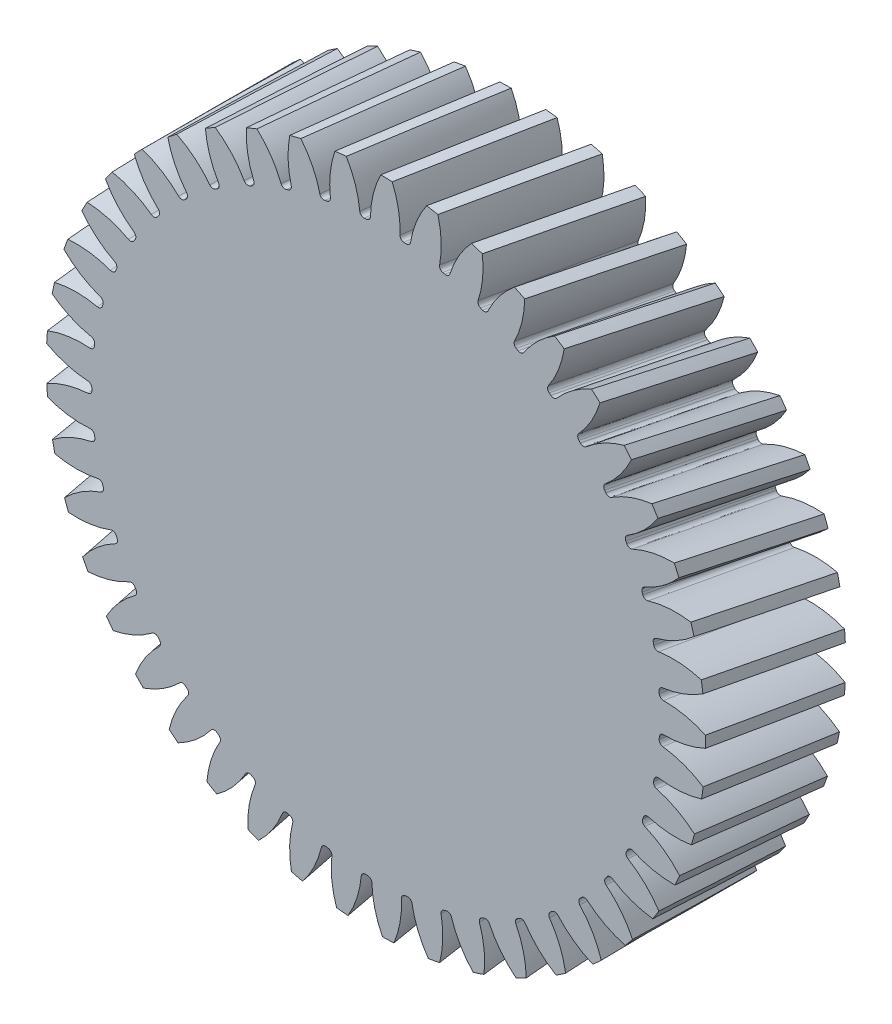
SolidWorks part; units mm, degrees
ref_plane "Front Plane" through (0, 0, 0) normal (0, 0, 1) x (1, 0, 0)
ref_plane "Top Plane" through (0, 0, 0) normal (0, 1, 0) x (1, 0, 0)
ref_plane "Right Plane" through (0, 0, 0) normal (1, 0, 0) x (0, 0, -1)
sketch "Sketch1" plane through (0, 0, 0) normal (0, 0, 1) x (1, 0, 0)
  circle A0 centre (0, 0) radius 33.75
  circle A1 centre (0, 0) radius 35.25
  circle A2 centre (0, 0) radius 30.375
  dimension "D1" = 67.5
  dimension "D2" = 70.5
  dimension "D3" = 3.375
extrude "Boss-Extrude1" add sketch "Sketch1" along normal mid plane 15 contours A1
sketch "Sketch2" plane through (0, 0, 0) normal (0, 0, 1) x (1, 0, 0)
  line L0 (0, 0) -> (0, 35.25) construction
  line L1 (-1.1779, 33.7294) -> (1.1779, 33.7294) construction
  line L2 (0, 0) -> (-0.5539, 30.37) construction
  line L3 (0, 30.4933) -> (-2.0737, 36.1906) construction
  line L4 (0, 0) -> (2.4589, 35.1641) construction
  line L5 (1.1779, 33.7294) -> (3.5278, 33.5651) construction
  circle A0 centre (0, 0) radius 35.25 construction
  arc A1 (-2.4531, 36.1669) -> (-0.5539, 30.37) centre (-10.9278, 30.1808) cw
  arc A2 (2.4531, 36.1669) -> (0.5539, 30.37) centre (10.9278, 30.1808) ccw
  circle A3 centre (0, 0) radius 30.375 construction
  arc A4 (0.5539, 30.37) -> (-0.5539, 30.37) centre (0, 0) ccw
  circle A5 centre (0, 0) radius 33.75 construction
  circle A6 centre (0, 0) radius 35.25 construction
  circle A7 centre (0, 0) radius 36.25
  arc A8 (2.4531, 36.1669) -> (-2.4531, 36.1669) centre (0, 0) ccw
  dimension "D2" = 20
  dimension "D3" = 4
  dimension "D1" = 1
sketch "Sketch7" plane through (0, 0, 0) normal (0, 1, 0) x (1, 0, 0)
  line L0 (-1.3225, -7.5) -> (1.3225, 7.5)
  line L1 (-35.25, -7.5) -> (35.25, -7.5) construction
  line L2 (35.25, 7.5) -> (-35.25, 7.5) construction
  line L3 (0, -8.25) -> (0, 8.25) construction
  dimension "D1" = 10
curve "Curve1"
sketch "Sketch8" plane through (0, 0, 7.5) normal (0, 0, 1) x (0.9993, 0.0375, 0)
  line L0 (0, 0) -> (0, 35.25) construction
  line L1 (-1.1779, 33.7294) -> (1.1779, 33.7294) construction
  line L2 (0, 0) -> (-0.5539, 30.37) construction
  line L3 (0, 30.4933) -> (-2.0737, 36.1906) construction
  line L4 (0, 0) -> (2.4589, 35.1641) construction
  line L5 (1.1779, 33.7294) -> (3.5278, 33.5651) construction
  arc A1 (-2.4531, 36.1669) -> (-0.5539, 30.37) centre (-10.9278, 30.1808) cw
  arc A2 (2.4531, 36.1669) -> (0.5539, 30.37) centre (10.9278, 30.1808) ccw
  arc A4 (0.5539, 30.37) -> (-0.5539, 30.37) centre (0, 0) ccw
  arc A8 (2.4531, 36.1669) -> (-2.4531, 36.1669) centre (0, 0) ccw
sketch "Sketch9" plane through (0, 0, -7.5) normal (0, 0, 1) x (0.9993, -0.0375, 0)
  line L0 (0, 0) -> (0, 35.25) construction
  line L1 (-1.1779, 33.7294) -> (1.1779, 33.7294) construction
  line L2 (0, 0) -> (-0.5539, 30.37) construction
  line L3 (0, 30.4933) -> (-2.0737, 36.1906) construction
  line L4 (0, 0) -> (2.4589, 35.1641) construction
  line L5 (1.1779, 33.7294) -> (3.5278, 33.5651) construction
  arc A1 (-2.4531, 36.1669) -> (-0.5539, 30.37) centre (-10.9278, 30.1808) cw
  arc A2 (2.4531, 36.1669) -> (0.5539, 30.37) centre (10.9278, 30.1808) ccw
  arc A4 (0.5539, 30.37) -> (-0.5539, 30.37) centre (0, 0) ccw
  arc A8 (2.4531, 36.1669) -> (-2.4531, 36.1669) centre (0, 0) ccw
loft "Cut-Loft1" cut profiles "Sketch8", "Sketch2", "Sketch9"
fillet "Fillet1" radius 0.45 2 edges
pattern_circular "CirPattern1" count 45 over 360 about axis through (0, 0, 7.5) along (0, 0, 1) of "Fillet1", "Cut-Loft1"
equation "\"Module\" = 1.5mm"
equation "\"Number of teeth\"= 45"
equation "\"D1@Sketch1\"=\"Module\"*\"Number of teeth\""
equation "\"D2@Sketch1\"=(\"Number of teeth\"+2) * \"Module\""
equation "\"D3@Sketch1\"=\"Module\" * if( \"Module\" =>1.25,2.25,2.4 )"
equation "\"D3@Sketch2\"=180 / \"Number of teeth\""
equation "\"D1@Fillet1\"=\"Module\"*.3"
equation "\"D1@CirPattern1\"=\"Number of teeth\""
